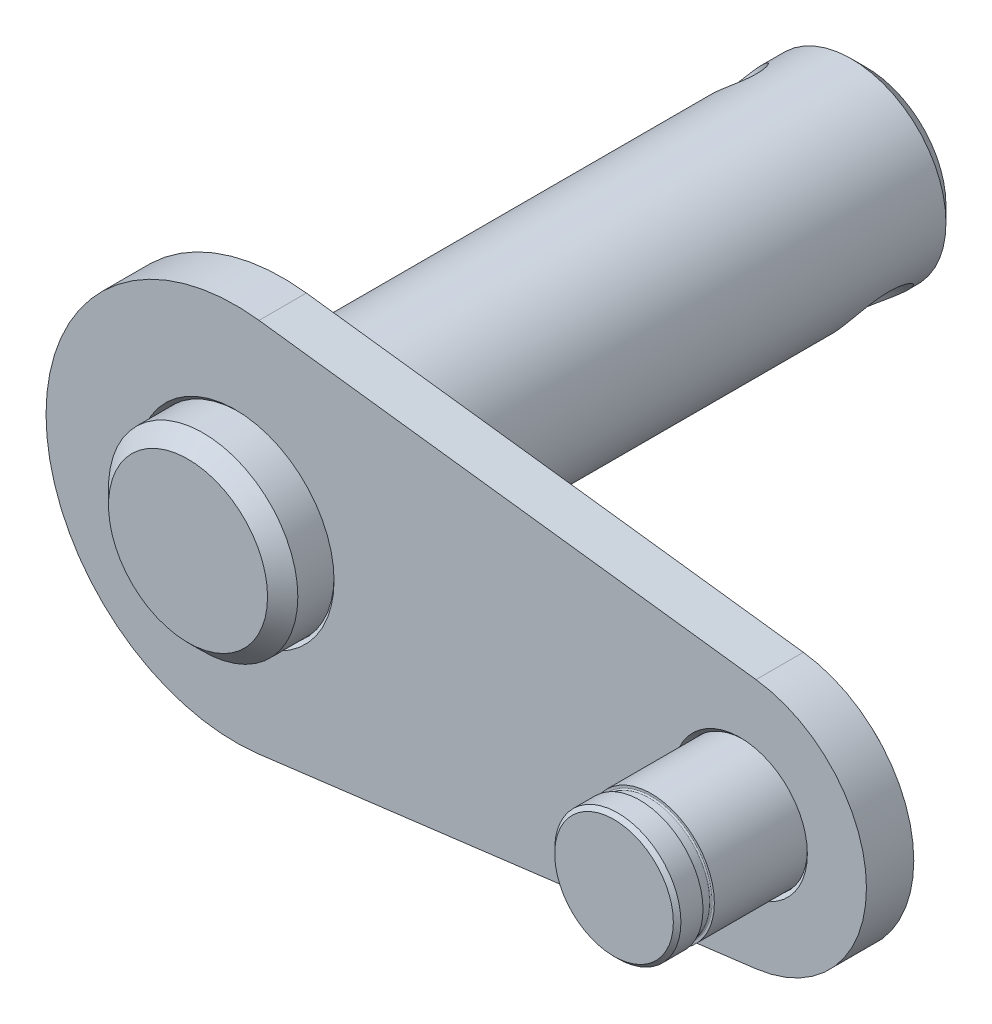
SolidWorks part; units mm, degrees
note: '?' marks a value the reader was unsure of.
other "DetailItem1"
other "DetailItem2"
other "Weld Folder"
other "Weld Bead1"
other "Weld Bead2"
ref_plane "Front Plane" through (0, 0, 0) normal (0, 0, 1) x (1, 0, 0)
ref_plane "Top Plane" through (0, 0, 0) normal (0, 1, 0) x (1, 0, 0)
ref_plane "Right Plane" through (0, 0, 0) normal (1, 0, 0) x (0, 0, -1)
sketch "Sketch1" plane through (0, 0, 0) normal (0, 0, 1) x (1, 0, 0)
  line L0 (52.3875, 12.6004) -> (2.3813, 18.9006)
  line L1 (2.3813, -18.9006) -> (52.3875, -12.6004)
  line L2 (0, 0) -> (50.8, 0) construction
  circle A0 centre (0, 0) radius 19.05
  circle A1 centre (50.8, 0) radius 12.7
  dimension "D1" = 38.1
  dimension "D2" = 25.4
  dimension "D3" = 50.8
extrude "Boss-Extrude1" add sketch "Sketch1" along normal mid plane 4.7625
sketch "Sketch2" plane through (0, 0, 2.3813) normal (0, 0, 1) x (1, 0, 0)
  circle A0 centre (0, 0) radius 9.525
  dimension "D1" = 19.05
extrude "Boss-Extrude2" add sketch "Sketch2" along normal blind 4.7625 and the other way blind 63.5 separate body
sketch "Sketch3" plane through (0, 0, 2.3813) normal (0, 0, 1) x (1, 0, 0)
  circle A0 centre (50.8, 0) radius 6.35
  dimension "D1" = 12.7
extrude "Boss-Extrude3" add sketch "Sketch3" along normal blind 12.7 and the other way offset from surface (9.525 mm away) 4.7625 separate body contours A0 other way up to face at (24.8047, 0, -2.3813)
sketch "Sketch4" plane through (0, 0, 2.3813) normal (0, 0, 1) x (1, 0, 0)
  circle A2 centre (50.8, 0) radius 6.3754
  circle A3 centre (0, 0) radius 9.525 construction
  circle A4 centre (0, 0) radius 9.5504
extrude "Cut-Extrude1" cut sketch "Sketch4" against normal through all
chamfer "Chamfer1" distance 1.524 angle 45 2 edges at (9.525, 0, 7.1438) (9.525, 0, -61.1187)
chamfer "Chamfer2" distance 0.381 angle 45 2 edges at (57.15, 0, 15.0812) (57.15, 0, -7.1438)
sketch3d "3DSketch1"
  point P0 (44.4528, 0.1874, -23.6404)
ref_axis "Axis1" through (50.8, 0, -6.7628) along (0, 0, 1)?
ref_plane "Plane5" through (0.0442, 1.4982, 0) normal (-0.0295, -0.9996, 0) x (-0.999, 0.0295, 0.035)
sketch "Groove Sketch" plane through (12.9156, 1.1183, -17.503) normal (-0.0295, -0.9996, 0) x (0.035, -0.001, 0.9994)
  line L0 (30.3612, -42.9858) -> (30.3692, -43.2142)
  line L1 (30.3692, -43.2142) -> (31.5115, -43.1742)
  line L2 (31.5115, -43.1742) -> (31.5035, -42.9457)
  line L3 (31.3722, -42.8233) -> (30.4837, -42.8544)
  line L4 (-0.4253, -37.939) -> (3.0733, -37.8165) construction
  line L5 (34.1001, -42.7023) -> (33.6822, -30.7716) construction
  line L6 (12.0605, -37.5017) -> (33.5104, -36.7503) construction
  arc A0 (30.4837, -42.8544) -> (30.3612, -42.9858) centre (30.4881, -42.9813) ccw
  arc A1 (31.3722, -42.8233) -> (31.5035, -42.9457) centre (31.3766, -42.9502) cw
  point P10 (30.9279, -42.8388)
  dimension "Radius" = 0.127
  dimension "ID" = 11.9888
  dimension "OD" = 12.7
  dimension "Width" = 1.143
  dimension "Location" = 3.175
revolve "Retaining Ring Groove" cut sketch "Groove Sketch" angle 360 about L4
other "lt duty ext spiral<1>"
chamfer "Chamfer3" distance 0.381 angle 45 4 edges at (57.1754, 0, -2.3813) (57.1754, 0, 2.3813) (9.5504, 0, -2.3813) (9.5504, 0, 2.3813)
ref_plane "Plane6" through (6.7352, -6.7352, 0) normal (0.7071, -0.7071, 0) x (0, 0, 1)
hole_wizard "1/4-20 Tapped Hole1" positions "Sketch8" profile "Sketch7" tap size "1/4-20" standard "ANSI Inch" end condition through all
sketch "Sketch8" plane through (6.7352, -6.7352, 0) normal (0.7071, -0.7071, 0) x (0, 0, 1)
  line L0 (-2.3813, 11.6809) -> (-2.3813, -28.1337) construction
  point P0 (-54.7687, 0)
  dimension "D1" = 52.3875
sketch "Sketch7" plane through (6.7352, -6.7352, -54.7687) normal (0, 0, 1) x (0.7071, 0.7071, 0)
  line L0 (0, 0) -> (0, 36.4658)
  line L1 (0, 36.4658) -> (3.81, 36.4658)
  line L2 (2.5527, 35.2085) -> (2.5527, 1.2573)
  line L3 (2.5527, 1.2573) -> (3.81, 0)
  line L5 (3.81, 0) -> (0, 0)
  line L6 (-2.5527, 1.2573) -> (-3.81, 0) construction
  line L7 (3.81, 36.4658) -> (2.5527, 35.2085)
  line L8 (-3.81, 36.4658) -> (-2.5527, 35.2085) construction
  line L11 (0, -6.35) -> (0, 107.95) construction
  dimension "Thru Tap Drill Dia." = 5.1054
  dimension "Thru Tap Drill Depth" = 36.4658
  dimension "Near C'Sink Dia." = 7.62
  dimension "Near C'Sink Angle" = 90
  dimension "Far C'Sink Dia." = 7.62
  dimension "Far C'Sink Angle" = 90
cosmetic thread "Hole Thread1" parameters "D2"=6.35
equation "\"D1@Sketch4\"=\"D1@Sketch2\"+.002"
equation "\"D2@Sketch4\"=\"D1@Sketch3\"+.002"
equation "\"D1@Sketch8\"=\"D2@Boss-Extrude2\"-.4375"
